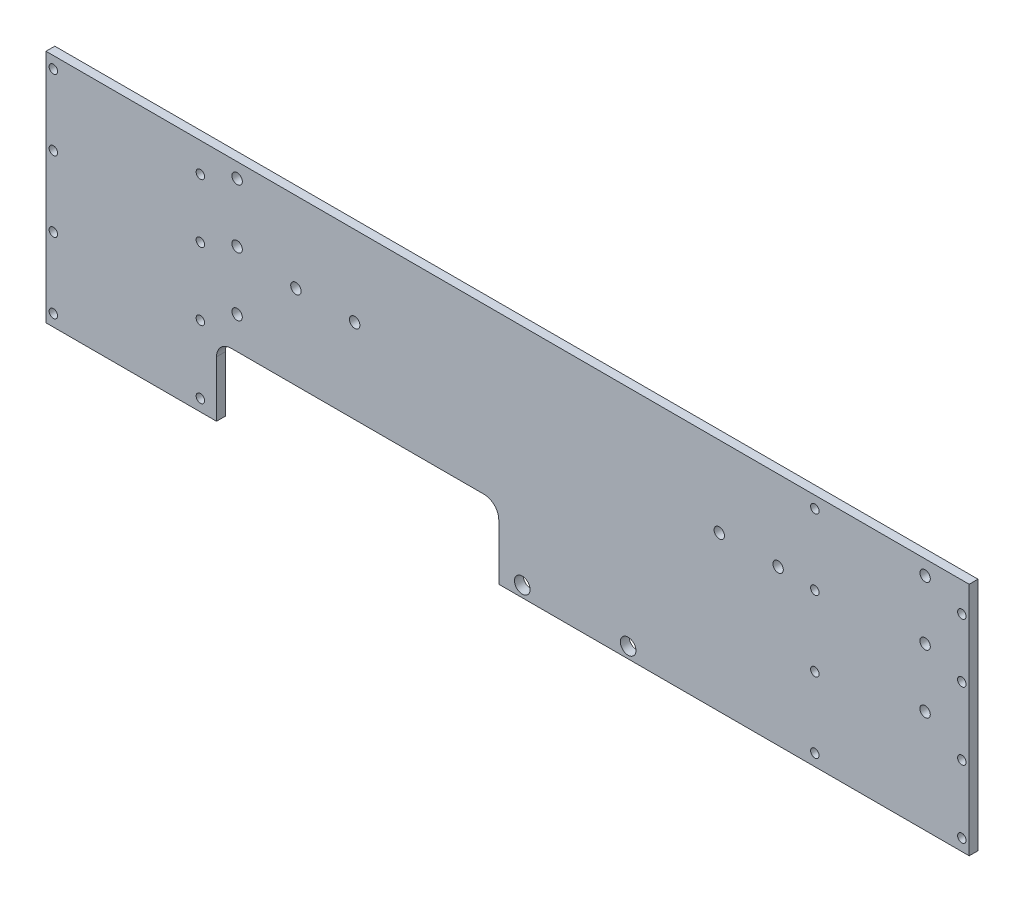
SolidWorks part; units mm, degrees
material "6061-T6 (SS)"
ref_plane "Front Plane" through (0, 0, 0) normal (0, 0, 1) x (1, 0, 0)
ref_plane "Top Plane" through (0, 0, 0) normal (0, 1, 0) x (1, 0, 0)
ref_plane "Right Plane" through (0, 0, 0) normal (1, 0, 0) x (0, 0, -1)
sketch "Sketch1" plane through (0, 0, 0) normal (0, 0, 1) x (1, 0, 0)
  line L1 (-199.39, 50.8) -> (199.39, 50.8)
  line L2 (-199.39, 50.8) -> (-199.39, -50.8)
  line L3 (-199.39, -50.8) -> (199.39, -50.8)
  line L4 (199.39, 50.8) -> (199.39, -50.8)
  line L5 (-199.39, 50.8) -> (199.39, -50.8) construction
  line L6 (-199.39, -50.8) -> (199.39, 50.8) construction
  point P0 (0, 0)
  dimension "D1" = 101.6
  dimension "D2" = 398.78
extrude "Boss-Extrude1" add sketch "Sketch1" along normal blind 3.81
sketch "Sketch11" plane through (0, 0, 3.81) normal (0, 0, 1) x (1, 0, 0)
  line L0 (-199.39, -50.8) -> (199.39, -50.8) construction
  line L1 (-125.73, -50.8) -> (-3.81, -50.8)
  line L2 (-125.73, -50.8) -> (-125.73, -20.32)
  line L3 (-125.73, -20.32) -> (-3.81, -20.32)
  line L4 (-3.81, -50.8) -> (-3.81, -20.32)
  line L5 (-199.39, 50.8) -> (-199.39, -50.8) construction
  line L6 (199.39, -50.8) -> (199.39, 50.8) construction
  dimension "D1" = 30.48
  dimension "D2" = 73.66
  dimension "D3" = 203.2
extrude "Cut-Extrude1" cut sketch "Sketch11" against normal through all
sketch "Sketch15" plane through (0, 0, 3.81) normal (0, 0, 1) x (1, 0, 0)
  line L0 (199.39, 50.8) -> (-199.39, 50.8) construction
  line L1 (91.44, 16.0648) -> (116.84, 16.0648) construction
  line L2 (180.34, 44.45) -> (180.34, -6.35) construction
  line L3 (199.39, -50.8) -> (199.39, 50.8) construction
  line L4 (199.39, 50.8) -> (-199.39, 50.8) construction
  line L5 (-199.39, 50.8) -> (-199.39, -50.8) construction
  line L6 (-66.04, 16.0648) -> (-91.44, 16.0648) construction
  line L7 (6.35, -46.0375) -> (52.07, -46.0375) construction
  line L8 (-3.81, -50.8) -> (199.39, -50.8) construction
  line L9 (-3.81, -50.8) -> (-3.81, -20.32) construction
  point P0 (196.215, 38.1)
  point P1 (196.215, 12.7)
  point P2 (196.215, -16.51)
  point P3 (196.215, -45.72)
  point P9 (132.715, -45.72)
  point P10 (180.34, 19.05)
  point P11 (132.715, -15.24)
  point P12 (132.715, 15.24)
  point P13 (132.715, 45.72)
  point P17 (91.44, 16.0648)
  point P20 (116.84, 16.0648)
  dimension "D1" = 63.5
  dimension "D2" = 3.175
  dimension "D3" = 29.21
  dimension "D4" = 29.21
  dimension "D5" = 25.4
  dimension "D6" = 5.08
  dimension "D7" = 30.48
  dimension "D8" = 30.48
  dimension "D9" = 30.48
  dimension "D10" = 19.05
  dimension "D11" = 50.8
  dimension "D12" = 6.35
  dimension "D13" = 25.4
  dimension "D14" = 34.7352
  dimension "D15" = 15.875
  dimension "D16" = 107.95
  dimension "D17" = 45.72
  dimension "D18" = 4.7625
  dimension "D19" = 10.16
hole_wizard "#6 Clearance Hole1" positions "Sketch19" profile "Sketch20" hole size "#6" standard "ANSI Inch" end condition through all
sketch "Sketch19" plane through (0, 0, 3.81) normal (0, 0, 1) x (1, 0, 0)
  point P18 (132.715, -15.24)
  point P21 (196.215, -16.51)
  point P24 (196.215, 12.7)
  point P27 (196.215, 38.1)
  point P30 (132.715, 45.72)
  point P33 (132.715, 15.24)
  point P55 (132.715, -45.72)
  point P58 (196.215, -45.72)
sketch "Sketch20" plane through (132.715, -15.24, 3.81) normal (1, 0, 0) x (0, -1, 0)
  line L0 (0, 0) -> (0, 3.81)
  line L1 (0, 3.81) -> (1.8288, 3.81)
  line L2 (1.8288, 3.81) -> (1.8288, 0)
  line L5 (1.8288, 0) -> (0, 0)
  line L11 (0, -6.35) -> (0, 107.95) construction
  dimension "Thru Hole Dia." = 3.6576
  dimension "Thru Hole Depth" = 3.81
hole_wizard "#8 Clearance Hole1" positions "Sketch24" profile "Sketch25" hole size "#8" standard "ANSI Inch" end condition through all
sketch "Sketch24" plane through (0, 0, 3.81) normal (0, 0, 1) x (1, 0, 0)
  line L0 (-199.39, 50.8) -> (-199.39, -50.8) construction
  point P0 (180.34, 44.45)
  point P3 (180.34, 19.05)
  point P6 (180.34, -6.35)
  point P10 (-116.84, 44.45)
  point P12 (-116.84, 19.05)
  point P14 (-116.84, -6.35)
  point P23 (91.44, 16.0648)
  point P26 (116.84, 16.0648)
  point P29 (-91.44, 16.0648)
  point P32 (-66.04, 16.0648)
  dimension "D1" = 82.55
sketch "Sketch25" plane through (180.34, 44.45, 3.81) normal (1, 0, 0) x (0, -1, 0)
  line L0 (0, 0) -> (0, 3.81)
  line L1 (0, 3.81) -> (2.2479, 3.81)
  line L2 (2.2479, 3.81) -> (2.2479, 0)
  line L5 (2.2479, 0) -> (0, 0)
  line L11 (0, -6.35) -> (0, 107.95) construction
  dimension "Thru Hole Dia." = 4.4958
  dimension "Thru Hole Depth" = 3.81
pattern_linear "LPattern1" count 2 spacing 328.93 along (-1, 0, 0) of "#6 Clearance Hole1"
fillet "Fillet1" radius 6.35 2 edges at (-125.73, -20.32, 1.905) (-3.81, -20.32, 1.905)
hole_wizard "1/4 Clearance Hole1" positions "Sketch26" profile "Sketch27" hole size "1/4" standard "ANSI Inch" end condition through all
sketch "Sketch26" plane through (0, 0, 3.81) normal (0, 0, 1) x (1, 0, 0)
  point P0 (6.35, -46.0375)
  point P3 (52.07, -46.0375)
sketch "Sketch27" plane through (6.35, -46.0375, 3.81) normal (1, 0, 0) x (0, -1, 0)
  line L0 (0, 0) -> (0, 3.81)
  line L1 (0, 3.81) -> (3.3782, 3.81)
  line L2 (3.3782, 3.81) -> (3.3782, 0)
  line L5 (3.3782, 0) -> (0, 0)
  line L11 (0, -6.35) -> (0, 107.95) construction
  dimension "Thru Hole Dia." = 6.7564
  dimension "Thru Hole Depth" = 3.81
